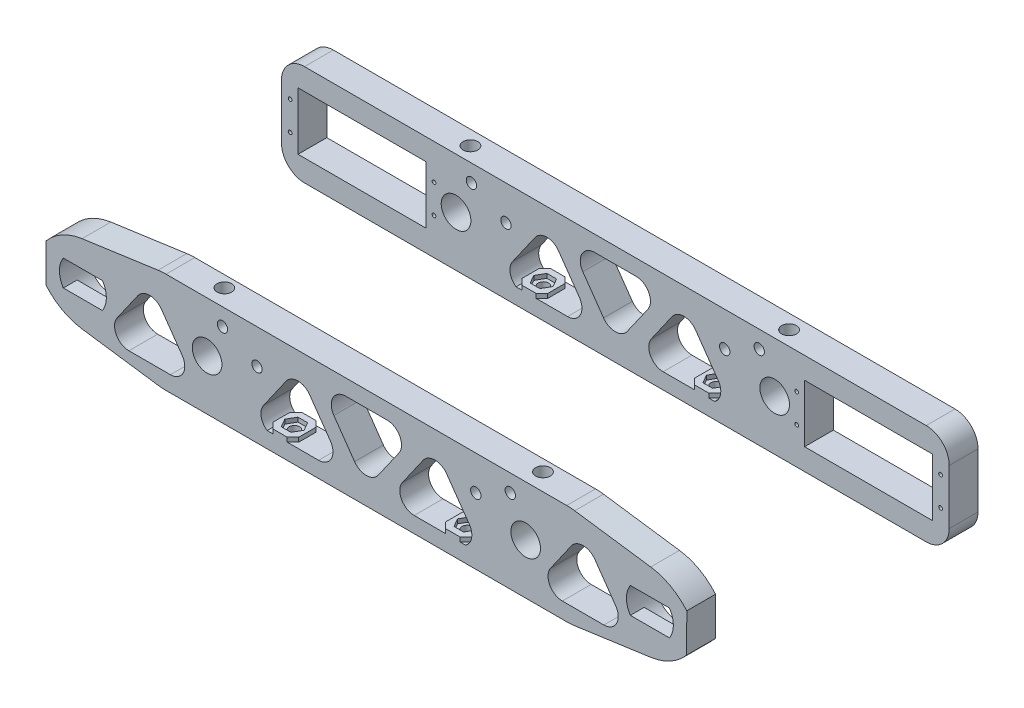
SolidWorks part; units mm, degrees
material "PLA 100% Infill"
ref_plane "Front Plane" through (0, 0, 0) normal (0, 0, 1) x (1, 0, 0)
ref_plane "Top Plane" through (0, 0, 0) normal (0, 1, 0) x (1, 0, 0)
ref_plane "Right Plane" through (0, 0, 0) normal (1, 0, 0) x (0, 0, -1)
sketch "Sketch1" plane through (0, 0, 0) normal (0, 0, 1) x (1, 0, 0)
  line L0 (-232, 17.5) -> (-148.2075, 17.5) construction
  line L1 (-232, 35) -> (0, 35)
  line L2 (-232, 35) -> (-232, 0)
  line L3 (-232, 0) -> (0, 0)
  line L4 (0, 35) -> (0, 0)
  line L5 (-116, 35) -> (-116, 17.5) construction
  line L6 (-156.61, 5.5) -> (-139.805, 29.5)
  line L7 (-139.805, 29.5) -> (-123, 5.5)
  line L8 (-123, 5.5) -> (-156.61, 5.5)
  line L9 (-132.805, 29.5) -> (-116, 5.5)
  line L10 (-116, 5.5) -> (-99.195, 29.5)
  line L11 (-99.195, 29.5) -> (-132.805, 29.5)
  line L12 (-139.805, 29.5) -> (-93.3936, 29.5) construction
  line L13 (-123, 5.5) -> (-123.2541, 5.5) construction
  line L14 (-74.6848, 5.5) -> (-74.6848, 29.5) construction
  line L21 (-116, 17.5) -> (-148.2075, 17.5) construction
  line L22 (-116, 17.5) -> (-83.7925, 17.5) construction
  line L23 (-92.195, 29.5) -> (-109, 5.5)
  line L24 (-75.39, 5.5) -> (-92.195, 29.5)
  line L25 (-109, 5.5) -> (-75.39, 5.5)
  line L27 (-116, 5.5) -> (-116, 0) construction
  circle A2 centre (-171.35, 17.5) radius 5.15
  circle A4 centre (-214.5, 17.5) radius 8.15
  circle A5 centre (-17.5, 17.5) radius 8.15
  circle A6 centre (-60.65, 17.5) radius 5.15
  point P12 (-176.5, 17.5)
  dimension "D2" = 35
  dimension "D3" = 16.3
  dimension "D4" = 10.3
  dimension "D5" = 232
  dimension "D6" = 43.15
  dimension "D7" = 24
  dimension "D9" = 7
  dimension "D10" = 110.7
  dimension "D8" = 70
extrude "Boss-Extrude1" add sketch "Sketch1" along normal blind 10 contours L4 A5 L1 L2 A4 L3 A2 A6 | A4 L2 | L4 A5 | A5 | A4 region at (-116, 32.6537, 0) region at (-214.5, 17.5, 0) region at (-17.5, 17.5, 0)
sketch "Sketch2" plane through (0, 0, 10) normal (0, 0, 1) x (1, 0, 0)
  circle A0 centre (-60.65, 17.5) radius 5.15 construction
  circle A1 centre (-60.65, 17.5) radius 5.15
  circle A2 centre (-171.35, 17.5) radius 5.15 construction
  circle A3 centre (-171.35, 17.5) radius 5.15
extrude "Boss-Extrude2" [suppressed] add sketch "Sketch2" against normal blind 2
ref_plane "Plane1" through (0, 0, -76.5) normal (0, 0, 1) x (1, 0, 0)
sketch "Sketch3" plane through (0, 0, -76.5) normal (0, 0, 1) x (1, 0, 0)
  line L0 (-232, 0) -> (0, 0) construction
  line L1 (-232, 35) -> (0, 35) construction
  line L2 (-232, 0) -> (0, 0)
  line L3 (-232, 35) -> (0, 35)
  line L4 (-181.75, 27.5) -> (-226.25, 27.5)
  line L5 (-181.75, 7.5) -> (-181.75, 27.5)
  line L6 (-226.25, 7.5) -> (-181.75, 7.5)
  line L7 (-226.25, 7.5) -> (-226.25, 27.5)
  line L8 (24, 17.5) -> (-237, 17.5) construction
  line L9 (-229, 22.7282) -> (-229, 12.7282) construction
  line L10 (-179, 22.7282) -> (-179, 12.7282) construction
  line L11 (-179, 12.7282) -> (-184.9311, 12.7282) construction
  line L12 (-116, 35) -> (-116, 0) construction
  line L13 (-50.25, 7.5) -> (-50.25, 27.5)
  line L14 (-5.75, 7.5) -> (-50.25, 7.5)
  line L15 (-5.75, 7.5) -> (-5.75, 27.5)
  line L16 (-50.25, 27.5) -> (-5.75, 27.5)
  line L18 (-92.195, 29.5) -> (-109, 5.5)
  line L21 (0, 35) -> (0, 0) construction
  line L22 (-232, 35) -> (-232, 0) construction
  line L23 (0, 35) -> (0, 0)
  line L24 (-232, 35) -> (-232, 0)
  line L31 (-116, 5.5) -> (-99.195, 29.5) construction
  line L32 (-99.195, 29.5) -> (-132.805, 29.5) construction
  line L33 (-132.805, 29.5) -> (-116, 5.5) construction
  line L34 (-123, 5.5) -> (-156.61, 5.5) construction
  line L35 (-139.805, 29.5) -> (-123, 5.5) construction
  line L36 (-156.61, 5.5) -> (-139.805, 29.5) construction
  line L43 (-116, 5.5) -> (-99.195, 29.5)
  line L44 (-99.195, 29.5) -> (-132.805, 29.5)
  line L45 (-132.805, 29.5) -> (-116, 5.5)
  line L46 (-123, 5.5) -> (-156.61, 5.5)
  line L47 (-139.805, 29.5) -> (-123, 5.5)
  line L48 (-156.61, 5.5) -> (-139.805, 29.5)
  line L49 (-75.39, 5.5) -> (-92.195, 29.5)
  line L50 (-109, 5.5) -> (-75.39, 5.5)
  circle A4 centre (-179, 12.7282) radius 0.65
  circle A5 centre (-179, 22.7282) radius 0.65
  circle A6 centre (-229, 12.7282) radius 0.65
  circle A7 centre (-229, 22.7282) radius 0.65
  circle A8 centre (-171.35, 17.5) radius 5.15 construction
  circle A9 centre (-171.35, 17.5) radius 5.15
  circle A10 centre (-3, 22.7282) radius 0.65
  circle A11 centre (-3, 12.7282) radius 0.65
  circle A12 centre (-53, 12.7282) radius 0.65
  circle A13 centre (-53, 22.7282) radius 0.65
  circle A14 centre (-60.65, 17.5) radius 5.15
  point P5 (-191.5, 17.5)
  point P21 (-181.75, 17.5)
  dimension "D10" = 1.3
  dimension "D1" = 2.75
  dimension "D2" = 20
  dimension "D3" = 44.5
  dimension "D4" = 2.75
  dimension "D5" = 10
  dimension "D6" = 5.2282
  dimension "D7" = 9.75
  dimension "D8" = 10
  dimension "D9" = 131.5
extrude "Boss-Extrude3" add sketch "Sketch3" against normal blind 10 separate body
sketch "Sketch4" plane through (0, 35, 0) normal (0, 1, 0) x (1, 0, 0)
  line L0 (-116, 86.5) -> (-116, -10) construction
  line L1 (0, 86.5) -> (-232, 86.5) construction
  line L2 (-232, -10) -> (0, -10) construction
  line L3 (-171.35, 86.5) -> (-171.35, -10) construction
  line L4 (-243.5, -4) -> (17.5, -4) construction
  line L5 (0, 86.5) -> (0, 76.5) construction
  line L6 (-232, 86.5) -> (-232, 76.5) construction
  line L7 (0, 81.5) -> (-232, 81.5) construction
  line L10 (-177.85, 39) -> (-122.5, 39) construction
  line L11 (-232, -10) -> (0, -10) construction
  circle A4 centre (-171.35, -4) radius 2.55
  circle A11 centre (-60.65, -4) radius 2.55
  circle A12 centre (-171.35, 81.5) radius 2.55
  circle A13 centre (-60.65, 81.5) radius 2.55
  dimension "D1" = 0
  dimension "D4" = 5.1
  dimension "D2" = 55.35
  dimension "D5" = 6
  dimension "D6" = 43
extrude "Cut-Extrude1" cut sketch "Sketch4" against normal blind 10
chamfer "Chamfer1" distance 45 angle 8 4 edges at (0, 35, 5) (0, 0, 5) (-232, 0, 5) (-232, 35, 5) first distance on face at (-171.35, 35, 6.55) first distance on face at (-116, 0, 5)
fillet "Fillet1" radius 8 4 edges at (0, 0, -81.5) (0, 35, -81.5) (-232, 0, -81.5) (-232, 35, -81.5)
sketch "Sketch6" plane through (0, 0, 10) normal (0, 0, 1) x (1, 0, 0)
  line L0 (-116, 5.5) -> (-99.195, 29.5) construction
  line L1 (-174.5, 5.5) -> (-208.11, 5.5)
  line L2 (-132.805, 29.5) -> (-116, 5.5) construction
  line L3 (-208.11, 5.5) -> (-191.305, 29.5)
  line L4 (-139.805, 29.5) -> (-123, 5.5) construction
  line L5 (-156.61, 5.5) -> (-139.805, 29.5) construction
  line L6 (-116, 5.5) -> (-99.195, 29.5)
  line L7 (-99.195, 29.5) -> (-132.805, 29.5)
  line L8 (-132.805, 29.5) -> (-116, 5.5)
  line L9 (-123, 5.5) -> (-156.61, 5.5)
  line L10 (-139.805, 29.5) -> (-123, 5.5)
  line L11 (-156.61, 5.5) -> (-139.805, 29.5)
  line L12 (-191.305, 29.5) -> (-174.5, 5.5)
  line L13 (-109, 5.5) -> (-75.39, 5.5) construction
  line L14 (-75.39, 5.5) -> (-92.195, 29.5) construction
  line L15 (-92.195, 29.5) -> (-109, 5.5) construction
  line L16 (-109, 5.5) -> (-75.39, 5.5)
  line L17 (-75.39, 5.5) -> (-92.195, 29.5)
  line L18 (-92.195, 29.5) -> (-109, 5.5)
  line L19 (-57.5, 5.5) -> (-23.89, 5.5)
  line L20 (-23.89, 5.5) -> (-40.695, 29.5)
  line L21 (-40.695, 29.5) -> (-57.5, 5.5)
  dimension "D3" = 51.5
  dimension "D4" = 51.5
  dimension "D1" = 2
  dimension "D2" = 2
extrude "Cut-Extrude3" cut sketch "Sketch6" against normal blind 10 contours L20 L21 L19 | L1 L3 L12 region at (-40.695, 13.5, 10)
sketch "Sketch7" plane through (0, 5.5, 0) normal (0, 1, 0) x (1, 0, 0)
  line L0 (-156.61, 81.5) -> (-75.39, 81.5) construction
  line L1 (-156.61, 86.5) -> (-156.61, 76.5) construction
  line L2 (-75.39, 86.5) -> (-75.39, 76.5) construction
  line L3 (-227.4452, 0) -> (-227.4452, 76.5) construction
  line L4 (-187, 0) -> (-45, 0) construction
  line L5 (-226.25, 76.5) -> (-181.75, 76.5) construction
  line L6 (-227.4452, 38.25) -> (0, 38.25) construction
  line L7 (0, 38.25) -> (0, 0) construction
  line L8 (-116, 81.5) -> (-116, -5) construction
  line L9 (-116, -10) -> (-116, 0) construction
  line L10 (-149.3486, 81.5) -> (-147.6743, 84.4)
  line L11 (-147.6743, 84.4) -> (-144.3257, 84.4)
  line L12 (-144.3257, 84.4) -> (-142.6514, 81.5)
  line L13 (-142.6514, 81.5) -> (-144.3257, 78.6)
  line L14 (-144.3257, 78.6) -> (-147.6743, 78.6)
  line L15 (-147.6743, 78.6) -> (-149.3486, 81.5)
  line L16 (-144.3257, 84.4) -> (-147.6743, 78.6) construction
  line L17 (-84.3257, 78.6) -> (-82.6514, 81.5)
  line L18 (-87.6743, 78.6) -> (-84.3257, 78.6)
  line L19 (-89.3486, 81.5) -> (-87.6743, 78.6)
  line L20 (-87.6743, 84.4) -> (-89.3486, 81.5)
  line L21 (-84.3257, 84.4) -> (-87.6743, 84.4)
  line L22 (-82.6514, 81.5) -> (-84.3257, 84.4)
  line L23 (-87.6743, -2.1) -> (-84.3257, -2.1)
  line L24 (-89.3486, -5) -> (-87.6743, -2.1)
  line L25 (-87.6743, -7.9) -> (-89.3486, -5)
  line L26 (-84.3257, -7.9) -> (-87.6743, -7.9)
  line L27 (-82.6514, -5) -> (-84.3257, -7.9)
  line L28 (-84.3257, -2.1) -> (-82.6514, -5)
  line L29 (-144.3257, -2.1) -> (-147.6743, -2.1)
  line L30 (-142.6514, -5) -> (-144.3257, -2.1)
  line L31 (-144.3257, -7.9) -> (-142.6514, -5)
  line L32 (-147.6743, -7.9) -> (-144.3257, -7.9)
  line L33 (-149.3486, -5) -> (-147.6743, -7.9)
  line L34 (-147.6743, -2.1) -> (-149.3486, -5)
  line L35 (-156.61, 86.5) -> (-123, 86.5) construction
  line L36 (-150.5, 86.5) -> (-141.5, 86.5)
  line L37 (-150.5, 86.5) -> (-150.5, 76.5)
  line L38 (-150.5, 76.5) -> (-141.5, 76.5)
  line L39 (-141.5, 86.5) -> (-141.5, 76.5)
  line L40 (-156.61, 76.5) -> (-123, 76.5) construction
  line L41 (-150.5, 86.5) -> (-141.5, 76.5) construction
  line L42 (-81.5, 76.5) -> (-90.5, 76.5)
  line L43 (-90.5, 86.5) -> (-90.5, 76.5)
  line L44 (-81.5, 86.5) -> (-90.5, 86.5)
  line L45 (-81.5, 86.5) -> (-81.5, 76.5)
  line L46 (-81.5, -10) -> (-81.5, 0)
  line L47 (-81.5, -10) -> (-90.5, -10)
  line L48 (-90.5, -10) -> (-90.5, 0)
  line L49 (-81.5, 0) -> (-90.5, 0)
  line L50 (-150.5, 0) -> (-141.5, 0)
  line L51 (-141.5, -10) -> (-141.5, 0)
  line L52 (-150.5, -10) -> (-141.5, -10)
  line L53 (-150.5, -10) -> (-150.5, 0)
  circle A2 centre (-146, 81.5) radius 1.8
  circle A3 centre (-86, 81.5) radius 1.8
  circle A4 centre (-86, -5) radius 1.8
  circle A5 centre (-146, -5) radius 1.8
  line M19 (-75.39, 0) -> (-109, 0)
  line M21 (-109, -10) -> (-75.39, -10)
  dimension "D1" = 30
  dimension "D2" = 3.6
  dimension "D3" = 5.8
  dimension "D4" = 9
extrude "Cut-Extrude4" cut sketch "Sketch7" against normal blind 10 contours A5 | A4 | A2 | A3 region at (-146, 5.5, -81.5) region at (-86, 5.5, -81.5) region at (-86, 5.5, 5) region at (-146, 5.5, 5)
extrude "Boss-Extrude4" add sketch "Sketch7<3>" along normal blind 1.5 contours L53 L52 L51 L50 L34 L29 L30 L31 L32 L33 | L48 L46 L23 L28 L27 L26 L25 L24 M21 M19 | L45 L44 L43 L42 L22 L17 L18 L19 L20 L21 | L39 L36 L37 L38 L14 L15 L10 L11 L12 L13 region at (-146, 5.5, -86.3655) region at (-86, 5.5, -76.6345) region at (-86, 5.5, 9.8655) region at (-146, 5.5, 0.1345)
sketch "Sketch7<3>" plane through (0, 5.5, 0) normal (0, 1, 0) x (1, 0, 0) same geometry as "Sketch7"
chamfer "Chamfer2" distance 2 angle 45 8 edges at (-90.5, 6.25, -76.5) (-81.5, 6.25, -76.5) (-81.5, 6.25, -86.5) (-90.5, 6.25, -86.5) (-141.5, 6.25, -86.5) (-150.5, 6.25, -86.5) (-141.5, 6.25, -76.5) (-150.5, 6.25, -76.5)
chamfer "Chamfer3" distance 2 angle 45 8 edges at (-81.5, 6.25, 0) (-81.5, 6.25, 10) (-90.5, 6.25, 10) (-90.5, 6.25, 0) (-141.5, 6.25, 0) (-141.5, 6.25, 10) (-150.5, 6.25, 10) (-150.5, 6.25, 0)
fillet "Fillet2" radius 20 8 edges at (-45, 35, 5) (-45, 0, 5) (0, 6.3243, 5) (0, 28.6757, 5) (-187, 0, 5) (-232, 6.3243, 5) (-232, 28.6757, 5) (-187, 35, 5)
extrude "Cut-Extrude5" cut sketch "Sketch1<3>" along normal blind 5.2 contours A4 | A5 region at (-214.5, 17.5, 0) region at (-17.5, 17.5, 0)
sketch "Sketch1<3>" plane through (0, 0, 0) normal (0, 0, 1) x (1, 0, 0) same geometry as "Sketch1"
sketch "Sketch8" plane through (0, 0, 0) normal (0, 0, -1) x (-1, 0, 0)
  line L0 (10.705, 22) -> (24.295, 22)
  line L1 (10.705, 13) -> (24.295, 13)
  line L2 (207.705, 22) -> (221.295, 22)
  line L3 (207.705, 13) -> (221.295, 13)
  circle A3 centre (214.5, 17.5) radius 8.15 construction
  arc A4 (207.705, 22) -> (207.705, 13) centre (214.5, 17.5) ccw
  circle A5 centre (17.5, 17.5) radius 8.15 construction
  arc A6 (10.705, 22) -> (10.705, 13) centre (17.5, 17.5) ccw
  arc A7 (24.295, 13) -> (24.295, 22) centre (17.5, 17.5) ccw
  arc A8 (221.295, 13) -> (221.295, 22) centre (214.5, 17.5) ccw
  dimension "D1" = 4.5
  dimension "D2" = 4.5
extrude "Cut-Extrude6" cut sketch "Sketch8" against normal through all
sketch "Sketch9" plane through (0, 25, 0) normal (0, 1, 0) x (1, 0, 0)
  line L0 (-60.65, 81.5) -> (-60.65, -4) construction
  line L1 (-60.65, -4) -> (-171.35, -4) construction
  line L2 (-116, -4) -> (-116, 76.5) construction
  line L3 (-60.65, 38.75) -> (-116, 38.75) construction
  circle A0 centre (-171.35, -4) radius 0.65
  circle A2 centre (-60.65, -4) radius 0.65
  circle A3 centre (-60.65, 81.5) radius 0.65
  circle A4 centre (-171.35, 81.5) radius 0.65
  dimension "D1" = 1.3
extrude "Cut-Extrude7" cut sketch "Sketch9" against normal blind 5.2
fillet "Fillet3" radius 5 9 edges at (-92.195, 29.5, -81.5) (-109, 5.5, -81.5) (-139.805, 29.5, -81.5) (-123, 5.5, -81.5) (-116, 5.5, -81.5) (-99.195, 29.5, -81.5) (-132.805, 29.5, -81.5) (-75.39, 5.5, -81.5) (-156.61, 5.5, -81.5)
fillet "Fillet4" radius 5 15 edges at (-191.305, 29.5, 5) (-139.805, 29.5, 5) (-92.195, 29.5, 5) (-40.695, 29.5, 5) (-174.5, 5.5, 5) (-123, 5.5, 5) (-23.89, 5.5, 5) (-208.11, 5.5, 5) (-109, 5.5, 5) (-57.5, 5.5, 5) (-75.39, 5.5, 5) (-156.61, 5.5, 5) (-132.805, 29.5, 5) (-99.195, 29.5, 5) (-116, 5.5, 5)
chamfer "Chamfer4" [suppressed] distance 8 angle 55
chamfer "Chamfer5" [suppressed] distance 8 angle 55
sketch "Sketch12" [suppressed] plane through (0, 22.9468, 0) normal (0, -1, 0) x (1, 0, 0)
  line L6 (-150.8936, 0) -> (-150.8936, 10)
  line L9 (-150.8936, 0) -> (-141.7164, 0)
  line L11 (-150.8936, 10) -> (-141.7164, 10)
  line L12 (-141.7164, 10) -> (-141.7164, 0)
  line L13 (-94.1064, 10) -> (-103.2836, 0) construction
  line L14 (-97.0071, 7.8765) -> (-100.3558, 7.8765)
  line L15 (-100.3558, 7.8765) -> (-102.0301, 4.9765)
  line L24 (-94.1064, 10) -> (-103.2836, 10)
  line L25 (-103.2836, 10) -> (-103.2836, 0)
  line L26 (-103.2836, 0) -> (-94.1064, 0)
  line L27 (-94.1064, 0) -> (-94.1064, 10)
  line L28 (-94.1064, 10) -> (-103.2836, 10)
  line L29 (-103.2836, 10) -> (-103.2836, 0)
  line L30 (-103.2836, 0) -> (-94.1064, 0)
  line L31 (-94.1064, 0) -> (-94.1064, 10)
  line L32 (-150.8936, -86.5) -> (-141.7164, -86.5)
  line L33 (-141.7164, -86.5) -> (-141.7164, -76.5)
  line L34 (-141.7164, -76.5) -> (-150.8936, -76.5)
  line L35 (-150.8936, -76.5) -> (-150.8936, -86.5)
  line L36 (-150.8936, -86.5) -> (-141.7164, -86.5)
  line L37 (-141.7164, -86.5) -> (-141.7164, -76.5)
  line L38 (-141.7164, -76.5) -> (-150.8936, -76.5)
  line L39 (-150.8936, -76.5) -> (-150.8936, -86.5)
  line L40 (-103.2836, -86.5) -> (-94.1064, -86.5)
  line L41 (-94.1064, -86.5) -> (-94.1064, -76.5)
  line L42 (-94.1064, -76.5) -> (-103.2836, -76.5)
  line L43 (-103.2836, -76.5) -> (-103.2836, -86.5)
  line L44 (-103.2836, -86.5) -> (-94.1064, -86.5)
  line L45 (-94.1064, -86.5) -> (-94.1064, -76.5)
  line L46 (-94.1064, -76.5) -> (-103.2836, -76.5)
  line L47 (-103.2836, -76.5) -> (-103.2836, -86.5)
  line L48 (-102.0301, 4.9765) -> (-100.3558, 2.0765)
  line L49 (-100.3558, 2.0765) -> (-97.0071, 2.0765)
  line L50 (-97.0071, 2.0765) -> (-95.3328, 4.9765)
  line L51 (-95.3328, 4.9765) -> (-97.0071, 7.8765)
  line L52 (-100.3558, 7.8765) -> (-97.0071, 2.0765) construction
  line L59 (-94.1064, -76.5) -> (-103.2836, -86.5) construction
  line L60 (-141.7164, -76.5) -> (-150.8936, -86.5) construction
  line L61 (-97.0207, -78.6) -> (-100.3693, -78.6)
  line L62 (-100.3693, -78.6) -> (-102.0437, -81.5)
  line L63 (-102.0437, -81.5) -> (-100.3693, -84.4)
  line L64 (-100.3693, -84.4) -> (-97.0207, -84.4)
  line L65 (-97.0207, -84.4) -> (-95.3464, -81.5)
  line L66 (-95.3464, -81.5) -> (-97.0207, -78.6)
  line L67 (-100.3693, -78.6) -> (-97.0207, -84.4) construction
  line L68 (-144.6307, -78.6) -> (-147.9793, -78.6)
  line L69 (-147.9793, -78.6) -> (-149.6536, -81.5)
  line L70 (-149.6536, -81.5) -> (-147.9793, -84.4)
  line L71 (-147.9793, -84.4) -> (-144.6307, -84.4)
  line L72 (-144.6307, -84.4) -> (-142.9563, -81.5)
  line L73 (-142.9563, -81.5) -> (-144.6307, -78.6)
  line L74 (-147.9793, -78.6) -> (-144.6307, -84.4) construction
  line L75 (-144.6307, 7.9) -> (-147.9793, 7.9)
  line L76 (-147.9793, 7.9) -> (-149.6536, 5)
  line L77 (-149.6536, 5) -> (-147.9793, 2.1)
  line L78 (-147.9793, 2.1) -> (-144.6307, 2.1)
  line L79 (-144.6307, 2.1) -> (-142.9563, 5)
  line L80 (-142.9563, 5) -> (-144.6307, 7.9)
  line L81 (-147.9793, 7.9) -> (-144.6307, 2.1) construction
  line L82 (-141.7164, 10) -> (-150.8936, 0) construction
  line L83 (-230.8579, 0) -> (-14.1421, 0) construction
  circle A1 centre (-98.695, 5) radius 1.8
  circle A3 centre (-98.695, -81.5) radius 1.8
  circle A4 centre (-146.305, -81.5) radius 1.8
  circle A5 centre (-146.305, 5) radius 1.8
  point P36 (-146.305, 5)
  point P57 (-146.305, 5)
  point P61 (-98.695, -81.5)
  point P64 (-146.305, -81.5)
  dimension "D1" = 3.6
  dimension "D5" = 3.6
  dimension "D12" = 3.6
  dimension "D16" = 3.6
  dimension "D2" = 5.8
  dimension "D3" = 5.8
  dimension "D4" = 5.8
  dimension "D10" = 5.8
  dimension "D11" = 5.8
  dimension "D6" = 5.8
  dimension "D13" = 5.8
  dimension "D14" = 5.8
  dimension "D15" = 5.8
  dimension "D17" = 5.8
  dimension "D18" = 5.8
  dimension "D19" = 5.8
  dimension "D7" = 0
  dimension "D8" = 0
  dimension "D9" = 0
extrude "Cut-Extrude8" [suppressed] cut sketch "Sketch12" against normal blind 1.5 contours L79 L80 L75 L76 L77 L78 A5 | A5 | L50 L51 L14 L15 L48 L49 A1 | A1 | L65 L66 L61 L62 L63 L64 A3 | A3 | L72 L73 L68 L69 L70 L71 A4 | A4
sketch "Sketch13" [suppressed] plane through (0, 22.9468, 0) normal (0, -1, 0) x (1, 0, 0)
  line L4 (-150.8936, -86.5) -> (-141.7164, -86.5)
  line L5 (-141.7164, -86.5) -> (-141.7164, -76.5)
  line L6 (-97.0071, 7.8765) -> (-100.3558, 7.8765)
  line L7 (-100.3558, 7.8765) -> (-102.0301, 4.9765)
  line L8 (-102.0301, 4.9765) -> (-100.3558, 2.0765)
  line L9 (-100.3558, 2.0765) -> (-97.0071, 2.0765)
  line L10 (-97.0071, 2.0765) -> (-95.3328, 4.9765)
  line L11 (-95.3328, 4.9765) -> (-97.0071, 7.8765)
  line L12 (-97.0071, 7.8765) -> (-100.3558, 7.8765)
  line L13 (-100.3558, 7.8765) -> (-102.0301, 4.9765)
  line L14 (-102.0301, 4.9765) -> (-100.3558, 2.0765)
  line L15 (-100.3558, 2.0765) -> (-97.0071, 2.0765)
  line L16 (-97.0071, 2.0765) -> (-95.3328, 4.9765)
  line L17 (-95.3328, 4.9765) -> (-97.0071, 7.8765)
  line L18 (-97.0207, -84.4) -> (-95.3464, -81.5)
  line L19 (-95.3464, -81.5) -> (-97.0207, -78.6)
  line L20 (-97.0207, -78.6) -> (-100.3693, -78.6)
  line L21 (-100.3693, -78.6) -> (-102.0437, -81.5)
  line L22 (-102.0437, -81.5) -> (-100.3693, -84.4)
  line L23 (-100.3693, -84.4) -> (-97.0207, -84.4)
  line L24 (-97.0207, -84.4) -> (-95.3464, -81.5)
  line L25 (-95.3464, -81.5) -> (-97.0207, -78.6)
  line L26 (-97.0207, -78.6) -> (-100.3693, -78.6)
  line L27 (-100.3693, -78.6) -> (-102.0437, -81.5)
  line L28 (-102.0437, -81.5) -> (-100.3693, -84.4)
  line L29 (-100.3693, -84.4) -> (-97.0207, -84.4)
  line L30 (-141.7164, -76.5) -> (-150.8936, -76.5)
  line L31 (-150.8936, -76.5) -> (-150.8936, -86.5)
  line L32 (-150.8936, -86.5) -> (-141.7164, -86.5)
  line L33 (-141.7164, -86.5) -> (-141.7164, -76.5)
  line L34 (-141.7164, -76.5) -> (-150.8936, -76.5)
  line L35 (-150.8936, -76.5) -> (-150.8936, -86.5)
  line L36 (-94.1064, 10) -> (-103.2836, 10)
  line L37 (-103.2836, 10) -> (-103.2836, 0)
  line L38 (-103.2836, 0) -> (-94.1064, 0)
  line L39 (-94.1064, 0) -> (-94.1064, 10)
  line L40 (-94.1064, 10) -> (-103.2836, 10)
  line L41 (-103.2836, 10) -> (-103.2836, 0)
  line L42 (-103.2836, 0) -> (-94.1064, 0)
  line L43 (-94.1064, 0) -> (-94.1064, 10)
  line L44 (-150.8936, 0) -> (-141.7164, 0)
  line L45 (-141.7164, 0) -> (-141.7164, 10)
  line L46 (-141.7164, 10) -> (-150.8936, 10)
  line L47 (-150.8936, 10) -> (-150.8936, 0)
  line L48 (-150.8936, 0) -> (-141.7164, 0)
  line L49 (-141.7164, 0) -> (-141.7164, 10)
  line L50 (-141.7164, 10) -> (-150.8936, 10)
  line L51 (-150.8936, 10) -> (-150.8936, 0)
  line L52 (-94.1064, -76.5) -> (-103.2836, -76.5)
  line L53 (-94.1064, -86.5) -> (-94.1064, -76.5)
  line L54 (-144.6307, -78.6) -> (-147.9793, -78.6)
  line L55 (-147.9793, -78.6) -> (-149.6536, -81.5)
  line L56 (-149.6536, -81.5) -> (-147.9793, -84.4)
  line L57 (-147.9793, -84.4) -> (-144.6307, -84.4)
  line L58 (-144.6307, -84.4) -> (-142.9563, -81.5)
  line L59 (-142.9563, -81.5) -> (-144.6307, -78.6)
  line L60 (-144.6307, -78.6) -> (-147.9793, -78.6)
  line L61 (-147.9793, -78.6) -> (-149.6536, -81.5)
  line L62 (-149.6536, -81.5) -> (-147.9793, -84.4)
  line L63 (-147.9793, -84.4) -> (-144.6307, -84.4)
  line L64 (-144.6307, -84.4) -> (-142.9563, -81.5)
  line L65 (-142.9563, -81.5) -> (-144.6307, -78.6)
  line L66 (-103.2836, -86.5) -> (-94.1064, -86.5)
  line L67 (-103.2836, -76.5) -> (-103.2836, -86.5)
  line L68 (-94.1064, -76.5) -> (-103.2836, -76.5)
  line L69 (-94.1064, -86.5) -> (-94.1064, -76.5)
  line L70 (-103.2836, -86.5) -> (-94.1064, -86.5)
  line L71 (-103.2836, -76.5) -> (-103.2836, -86.5)
  line L74 (-144.6307, 7.9) -> (-147.9793, 7.9)
  line L75 (-147.9793, 7.9) -> (-149.6536, 5)
  line L76 (-149.6536, 5) -> (-147.9793, 2.1)
  line L77 (-147.9793, 2.1) -> (-144.6307, 2.1)
  line L78 (-144.6307, 2.1) -> (-142.9563, 5)
  line L79 (-142.9563, 5) -> (-144.6307, 7.9)
  line L80 (-144.6307, 7.9) -> (-147.9793, 7.9)
  line L81 (-147.9793, 7.9) -> (-149.6536, 5)
  line L82 (-149.6536, 5) -> (-147.9793, 2.1)
  line L83 (-147.9793, 2.1) -> (-144.6307, 2.1)
  line L84 (-144.6307, 2.1) -> (-142.9563, 5)
  line L85 (-142.9563, 5) -> (-144.6307, 7.9)
  circle A1 centre (-98.695, -81.5) radius 1.8
  circle A2 centre (-98.695, -81.5) radius 1.8
  circle A3 centre (-98.695, 5) radius 1.8
  circle A4 centre (-98.695, 5) radius 1.8
  circle A5 centre (-146.305, -81.5) radius 1.8
  circle A6 centre (-146.305, -81.5) radius 1.8
  circle A7 centre (-146.305, 5) radius 1.8
  circle A8 centre (-146.305, 5) radius 1.8
  dimension "D1" = 0
  dimension "D2" = 0
  dimension "D3" = 0
  dimension "D4" = 0
  dimension "D5" = 0
  dimension "D6" = 0
  dimension "D7" = 0
  dimension "D8" = 0
  dimension "D9" = 0
  dimension "D10" = 0
  dimension "D11" = 0
  dimension "D12" = 0
extrude "Cut-Extrude9" [suppressed] cut sketch "Sketch13" against normal through all contours A4 | A8 | A6 | A2
fillet "Fillet5" [suppressed] radius 5
chamfer "Chamfer6" distance 12 angle 18 2 edges at (-231.0114, 17.5, 5) (-0.9886, 17.5, 5) first distance on face at (-223.8706, 9.5407, 5) first distance on face at (-8.1294, 9.5407, 5)
sketch "Sketch14" plane through (0, 0, -86.5) normal (0, 0, -1) x (-1, 0, 0)
  line L0 (116, 35) -> (116, 0) construction
  line L1 (8, 35) -> (224, 35) construction
  line L2 (224, 0) -> (8, 0) construction
  circle A0 centre (78, 23) radius 1.8
  circle A1 centre (66, 29) radius 1.8
  circle A2 centre (166, 29) radius 1.8
  circle A3 centre (154, 23) radius 1.8
  dimension "D1" = 3.6
  dimension "D2" = 3.6
  dimension "D3" = 6
  dimension "D4" = 38
  dimension "D5" = 12
  dimension "D6" = 23
extrude "Cut-Extrude10" cut sketch "Sketch14" against normal through all
